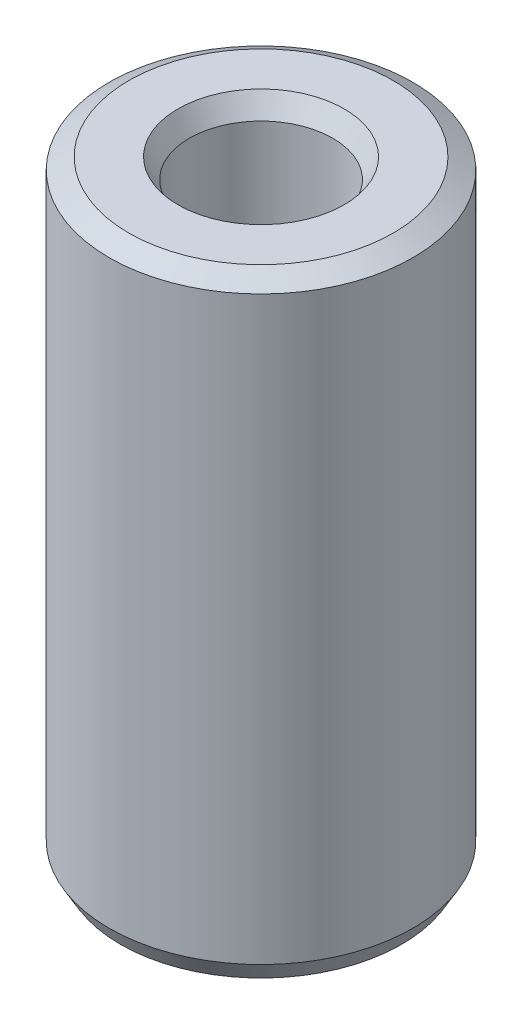
SolidWorks part; units mm, degrees
ref_plane "Front Plane" through (0, 0, 0) normal (0, 0, 1) x (1, 0, 0)
ref_plane "Top Plane" through (0, 0, 0) normal (0, 1, 0) x (1, 0, 0)
ref_plane "Right Plane" through (0, 0, 0) normal (1, 0, 0) x (0, 0, -1)
sketch "Sketch1" plane through (0, 0, 0) normal (0, 1, 0) x (1, 0, 0)
  circle A0 centre (0, 0) radius 50
  dimension "SLEEVE_OD" = 100
extrude "Boss-Extrude1" add sketch "Sketch1" along normal blind 201.3971
sketch "Sketch2" plane through (0, 0, 0) normal (0, 1, 0) x (1, 0, 0)
  circle A0 centre (0, 0) radius 23.6101
  dimension "BORE_D" = 47.2201
extrude "Cut-Extrude1" cut sketch "Sketch2" along normal through all
chamfer "Chamfer1" distance 3.7505 angle 60 4 edges at (0, 201.3971, 23.6101) (0, 0, 23.6101) (0, 0, 50) (0, 201.3971, 50) first distance on face at (0, 201.3971, 23.6101) first distance on face at (0, 0, 23.6101) first distance on face at (0, 201.3971, 50)
